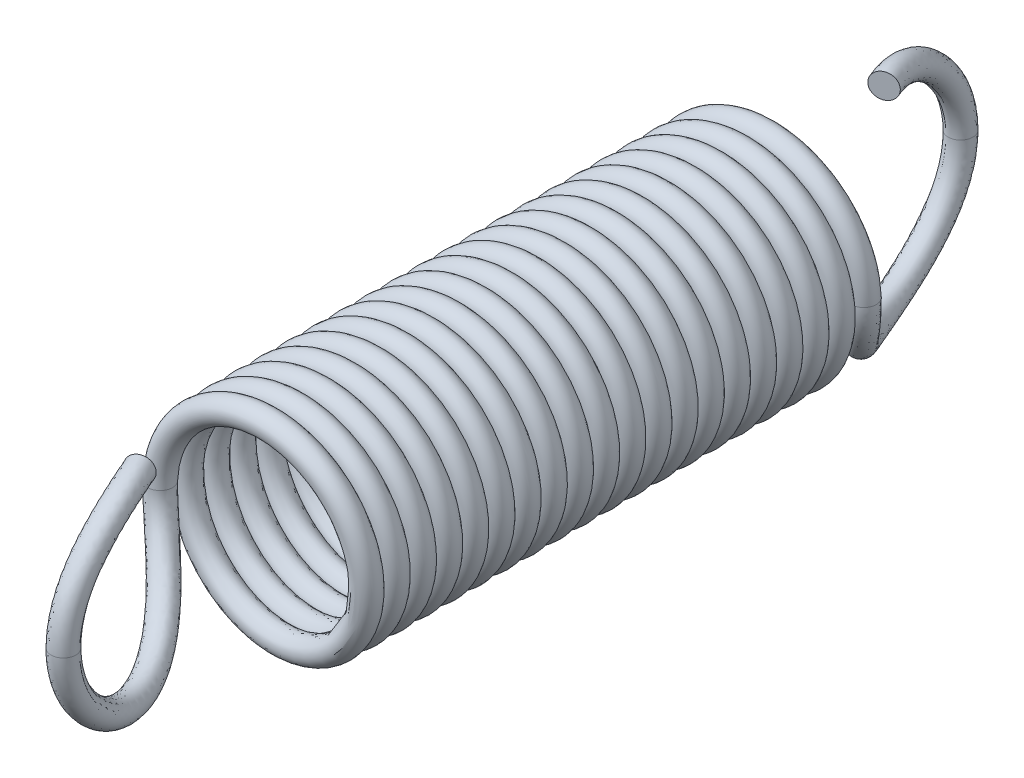
SolidWorks part; units mm, degrees
note: '?' marks a value the reader was unsure of.
ref_plane "Front Plane" through (0, 0, 0) normal (0, 0, 1) x (1, 0, 0)
ref_plane "Top Plane" through (0, 0, 0) normal (0, 1, 0) x (1, 0, 0)
ref_plane "Right Plane" through (0, 0, 0) normal (1, 0, 0) x (0, 0, -1)
sketch "Sketch1" plane through (0, 0, 0) normal (1, 0, 0) x (0, 0, -1)
  line L0 (-38.1, 0) -> (38.1, 0) construction
  line L1 (38.1, 0) -> (78.74, 0) construction
  line L2 (-38.1, 9.525) -> (-38.1, -9.525) construction
  point P4 (0, 0)
  point P6 (-35.941, 0)
  point P9 (-38.1, 0)
  dimension "Spring OD" = 19.05
  dimension "Wire OD" = 2.159
  dimension "Overall Length" = 76.2
  dimension "Extended Length" = 116.84
sketch "Sketch2" plane through (0, 0, 0) normal (1, 0, 0) x (0, 0, -1)
  line L1 (-40.259, 0) -> (-38.1, 0) construction
  line L2 (-30.734, -7.366) -> (-30.734, -9.525) construction
  line L3 (0, 0) -> (0, 9.525) construction
  line L4 (-38.1, 0) -> (-35.941, 0) construction
  line L5 (-38.1, 0) -> (38.1, 0) construction
  line L6 (30.734, -7.366) -> (30.734, -9.525) construction
  line L7 (40.259, 0) -> (38.1, 0) construction
  line L8 (-30.734, -7.366) -> (30.734, -7.366) construction
  line L9 (-30.734, -9.525) -> (30.734, -9.525) construction
  line L10 (-23.368, 0) -> (-21.209, 0) construction
  line L11 (21.209, 0) -> (23.368, 0) construction
  circle A0 centre (-30.734, 0) radius 9.525 construction
  circle A2 centre (-30.734, 0) radius 7.366 construction
  circle A3 centre (30.734, 0) radius 7.366 construction
  circle A4 centre (30.734, 0) radius 9.525 construction
  point P2 (-12.573, 0)
  point P3 (12.573, 0)
  point P10 (-39.1795, 0)
  point P22 (-30.734, -8.4455)
  point P28 (39.1795, 0)
  point P33 (-22.2885, 0)
  point P34 (22.2885, 0)
  dimension "OD" = 19.05
  dimension "D1" = 44.577
  dimension "D2" = 8.636
  dimension "D3" = 8.636
ref_plane "Plane1" through (0, 0, 22.2885) normal (0, 0, 1) x (1, 0, 0)
sketch "Sketch3" plane through (0, 0, 22.2885) normal (0, 0, 1) x (1, 0, 0)
  circle A0 centre (0, 0) radius 8.4455
curve "Helix/Spiral1" pitch 2.286 height 44.577 turns 19.5 parameters "Height"=44.577, "Pitch"=2.286
sketch "Sketch4" plane through (0, 0, 0) normal (0, 1, 0) x (1, 0, 0)
  line L0 (-0.55, -22.2885) -> (0.55, -22.2885) construction
  circle A0 centre (-8.4455, -22.2885) radius 1.0795
  dimension "D1" = 2.159
sweep "Spring Body Sweep" add profiles "Sketch4" path "Helix/Spiral1"
sketch "Sketch5" plane through (0, 0, 0) normal (1, 0, 0) x (0, 0, -1)
  line L2 (-38.1, 0) -> (38.1, 0) construction
  arc A1 (-22.2885, 0) -> (-30.734, 8.4455) centre (-30.734, 0) cw
sketch "Sketch6" plane through (0, 0, 0) normal (0, 1, 0) x (1, 0, 0)
  line L1 (-8.4455, -22.2885) -> (8.4455, -22.2885) construction
  line L2 (0, -22.2885) -> (0, -39.1795) construction
  arc A2 (-8.4455, -22.2885) -> (0, -39.1795) centre (-21.1138, -39.1795) cw
curve "Curve1"
sketch "Sketch7" plane through (0, 0, 0) normal (0, -1, 0) x (1, 0, 0)
  circle A1 centre (-8.4455, 22.2885) radius 1.0795
  circle A2 centre (-8.4455, 22.2885) radius 1.0795
  dimension "D1" = 0
sweep "Spring Hook Sweep" add profiles "Sketch7" path "Curve1"
curve "Curve1"
ref_axis "Axis1" through (0, 7.5606, 0) along (0, -1, 0)
pattern_circular "Spring Hook CirPattern" count 2 over 360 about axis through (0, 7.5606, 0) along (0, -1, 0) of "Spring Hook Sweep"
ref_axis "Center Axis 1" through (0, 0, -57.0156) along (0, 0, 1)?
ref_plane "Contact Plane 1" through (0, 0, 38.1) normal (0, 0, 1) x (1, 0, 0)
ref_plane "Contact Plane 2" through (0, 0, -38.1) normal (0, 0, 1) x (1, 0, 0)
equation "\"D1@Sketch4\" = \"Wire OD@Sketch1\""
equation "\"Height@Helix/Spiral1\"=\"D1@Sketch2\""
equation "\"D2@Sketch2\"=4*\"Wire OD@Sketch1\""
equation "\"D3@Sketch2\"=\"D2@Sketch2\""
